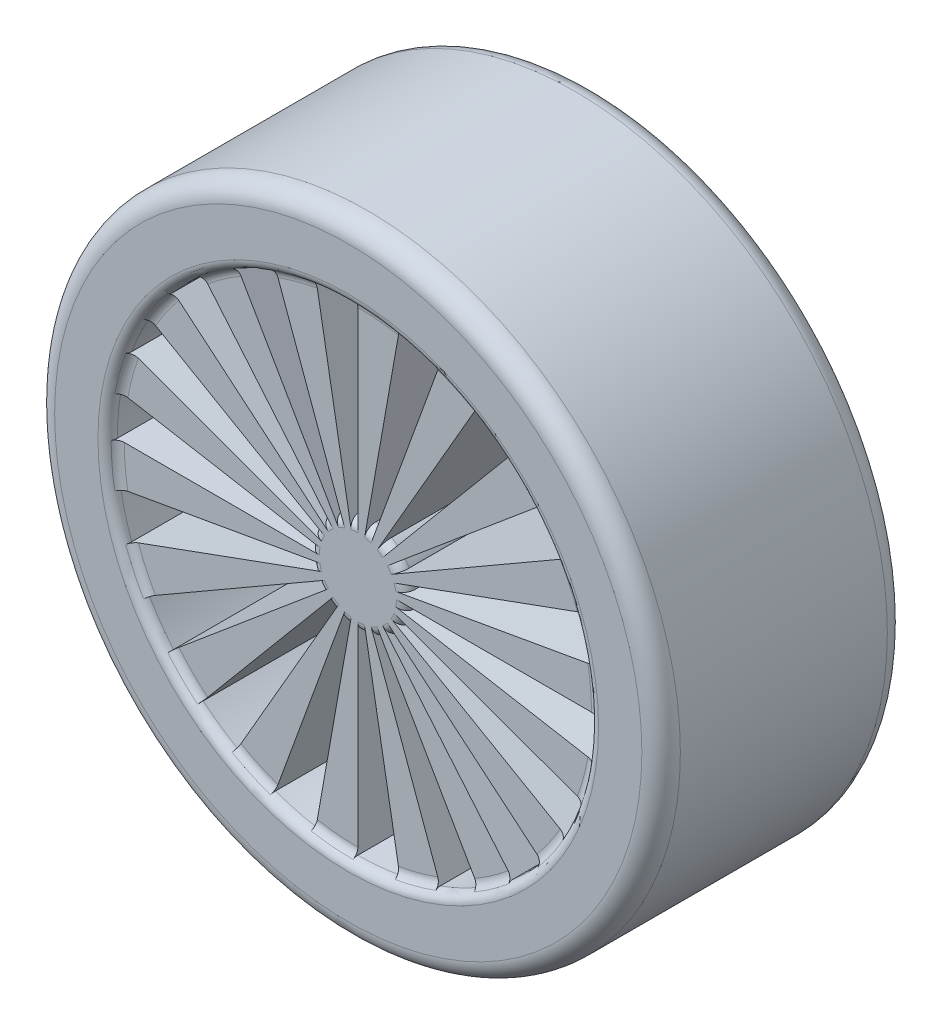
SolidWorks part; units mm, degrees
ref_plane "前视基准面" through (0, 0, 0) normal (0, 0, 1) x (1, 0, 0)
ref_plane "上视基准面" through (0, 0, 0) normal (0, 1, 0) x (1, 0, 0)
ref_plane "右视基准面" through (0, 0, 0) normal (1, 0, 0) x (0, 0, -1)
sketch "草图1" plane through (0, 0, 0) normal (0, 0, 1) x (1, 0, 0)
  circle A0 centre (0, 0) radius 32.5
  dimension "D1" = 65
extrude "凸台-拉伸1" add sketch "草图1" along normal blind 25.5
fillet "圆角1" radius 2 2 edges at (32.5, 0, 25.5) (32.5, 0, 0)
sketch "草图2" plane through (0, 0, 0) normal (0, 0, -1) x (-1, 0, 0)
  circle A0 centre (0, 0) radius 25
  dimension "D1" = 50
extrude "切除-拉伸1" cut sketch "草图2" against normal blind 8 contours A0
fillet "圆角2" radius 1 1 edges at (-25, 0, 0)
sketch "草图3" plane through (0, 0, 8) normal (0, 0, -1) x (-1, 0, 0)
  line L0 (0, 5) -> (0, 25)
  line L1 (0.8682, 4.924) -> (4.3412, 24.6202)
  line L2 (0.8682, 4.924) -> (0, 0) construction
  line L3 (1.7101, 4.6985) -> (8.5505, 23.4923)
  line L4 (2.5, 4.3301) -> (12.5, 21.6506)
  line L5 (3.2139, 3.8302) -> (16.0697, 19.1511)
  line L6 (3.8302, 3.2139) -> (19.1511, 16.0697)
  line L7 (4.3301, 2.5) -> (21.6506, 12.5)
  line L8 (4.6985, 1.7101) -> (23.4923, 8.5505)
  line L9 (4.924, 0.8682) -> (24.6202, 4.3412)
  line L10 (5, 0) -> (25, 0)
  line L11 (4.924, -0.8682) -> (24.6202, -4.3412)
  line L12 (4.6985, -1.7101) -> (23.4923, -8.5505)
  line L13 (4.3301, -2.5) -> (21.6506, -12.5)
  line L14 (3.8302, -3.2139) -> (19.1511, -16.0697)
  line L15 (3.2139, -3.8302) -> (16.0697, -19.1511)
  line L16 (2.5, -4.3301) -> (12.5, -21.6506)
  line L17 (1.7101, -4.6985) -> (8.5505, -23.4923)
  line L18 (0.8682, -4.924) -> (4.3412, -24.6202)
  line L19 (0, -5) -> (0, -25)
  line L20 (-0.8682, -4.924) -> (-4.3412, -24.6202)
  line L21 (-1.7101, -4.6985) -> (-8.5505, -23.4923)
  line L22 (-2.5, -4.3301) -> (-12.5, -21.6506)
  line L23 (-3.2139, -3.8302) -> (-16.0697, -19.1511)
  line L24 (-3.8302, -3.2139) -> (-19.1511, -16.0697)
  line L25 (-4.3301, -2.5) -> (-21.6506, -12.5)
  line L26 (-4.6985, -1.7101) -> (-23.4923, -8.5505)
  line L27 (-4.924, -0.8682) -> (-24.6202, -4.3412)
  line L28 (-5, 0) -> (-25, 0)
  line L29 (-4.924, 0.8682) -> (-24.6202, 4.3412)
  line L30 (-4.6985, 1.7101) -> (-23.4923, 8.5505)
  line L31 (-4.3301, 2.5) -> (-21.6506, 12.5)
  line L32 (-3.8302, 3.2139) -> (-19.1511, 16.0697)
  line L33 (-3.2139, 3.8302) -> (-16.0697, 19.1511)
  line L34 (-2.5, 4.3301) -> (-12.5, 21.6506)
  line L35 (-1.7101, 4.6985) -> (-8.5505, 23.4923)
  line L36 (-0.8682, 4.924) -> (-4.3412, 24.6202)
  arc A0 (-0.8682, 4.924) -> (-1.7101, 4.6985) centre (0, 0) ccw
  circle A1 centre (0, 0) radius 25 construction
  arc A2 (4.3412, 24.6202) -> (0, 25) centre (0, 0) ccw
  arc A3 (12.5, 21.6506) -> (8.5505, 23.4923) centre (0, 0) ccw
  arc A4 (19.1511, 16.0697) -> (16.0697, 19.1511) centre (0, 0) ccw
  arc A5 (23.4923, 8.5505) -> (21.6506, 12.5) centre (0, 0) ccw
  arc A6 (25, 0) -> (24.6202, 4.3412) centre (0, 0) ccw
  arc A7 (23.4923, -8.5505) -> (24.6202, -4.3412) centre (0, 0) ccw
  arc A8 (19.1511, -16.0697) -> (21.6506, -12.5) centre (0, 0) ccw
  arc A9 (12.5, -21.6506) -> (16.0697, -19.1511) centre (0, 0) ccw
  arc A10 (4.3412, -24.6202) -> (8.5505, -23.4923) centre (0, 0) ccw
  arc A11 (-4.3412, -24.6202) -> (0, -25) centre (0, 0) ccw
  arc A12 (-12.5, -21.6506) -> (-8.5505, -23.4923) centre (0, 0) ccw
  arc A13 (-19.1511, -16.0697) -> (-16.0697, -19.1511) centre (0, 0) ccw
  arc A14 (-23.4923, -8.5505) -> (-21.6506, -12.5) centre (0, 0) ccw
  arc A15 (-25, 0) -> (-24.6202, -4.3412) centre (0, 0) ccw
  arc A16 (-23.4923, 8.5505) -> (-24.6202, 4.3412) centre (0, 0) ccw
  arc A17 (-19.1511, 16.0697) -> (-21.6506, 12.5) centre (0, 0) ccw
  arc A18 (-12.5, 21.6506) -> (-16.0697, 19.1511) centre (0, 0) ccw
  arc A19 (-4.3412, 24.6202) -> (-8.5505, 23.4923) centre (0, 0) ccw
  arc A20 (0.8682, 4.924) -> (0, 5) centre (0, 0) ccw
  arc A21 (2.5, 4.3301) -> (1.7101, 4.6985) centre (0, 0) ccw
  arc A22 (3.8302, 3.2139) -> (3.2139, 3.8302) centre (0, 0) ccw
  arc A23 (4.6985, 1.7101) -> (4.3301, 2.5) centre (0, 0) ccw
  arc A24 (5, 0) -> (4.924, 0.8682) centre (0, 0) ccw
  arc A25 (4.6985, -1.7101) -> (4.924, -0.8682) centre (0, 0) ccw
  arc A26 (3.8302, -3.2139) -> (4.3301, -2.5) centre (0, 0) ccw
  arc A27 (2.5, -4.3301) -> (3.2139, -3.8302) centre (0, 0) ccw
  arc A28 (0.8682, -4.924) -> (1.7101, -4.6985) centre (0, 0) ccw
  arc A29 (-0.8682, -4.924) -> (0, -5) centre (0, 0) ccw
  arc A30 (-2.5, -4.3301) -> (-1.7101, -4.6985) centre (0, 0) ccw
  arc A31 (-3.8302, -3.2139) -> (-3.2139, -3.8302) centre (0, 0) ccw
  arc A32 (-4.6985, -1.7101) -> (-4.3301, -2.5) centre (0, 0) ccw
  arc A33 (-5, 0) -> (-4.924, -0.8682) centre (0, 0) ccw
  arc A34 (-4.6985, 1.7101) -> (-4.924, 0.8682) centre (0, 0) ccw
  arc A35 (-3.8302, 3.2139) -> (-4.3301, 2.5) centre (0, 0) ccw
  arc A36 (-2.5, 4.3301) -> (-3.2139, 3.8302) centre (0, 0) ccw
  point P81 (0, 0)
  dimension "D1" = 10
  dimension "D2" = 18
  dimension "D3" = 10
extrude "切除-拉伸2" cut sketch "草图3" against normal through all
sketch "草图4" plane through (0, 0, 25.5) normal (0, 0, 1) x (1, 0, 0)
  circle A0 centre (0, 0) radius 25
  dimension "D1" = 50
extrude "切除-拉伸3" cut sketch "草图4" against normal blind 1
fillet "圆角3" radius 1 1 edges at (-25, 0, 25.5)
fillet "圆角4" radius 1 18 edges at (-2.1131, 4.5315, 24.5) (-3.5355, 3.5355, 24.5) (-4.5315, 2.1131, 24.5) (-4.981, 0.4358, 24.5) (-4.8296, -1.2941, 24.5) (-4.0958, -2.8679, 24.5) (-2.8679, -4.0958, 24.5) (-1.2941, -4.8296, 24.5) (0.4358, -4.981, 24.5) (2.1131, -4.5315, 24.5) (3.5355, -3.5355, 24.5) (4.5315, -2.1131, 24.5) (4.981, -0.4358, 24.5) (4.8296, 1.2941, 24.5) (4.0958, 2.8679, 24.5) (2.8679, 4.0958, 24.5) (1.2941, 4.8296, 24.5) (-0.4358, 4.981, 24.5)
fillet "圆角5" radius 1 1 edges at (6.4705, -24.1481, 24.5)
fillet "圆角6" radius 1 17 edges at (-2.1789, -24.9049, 24.5) (-10.5655, -22.6577, 24.5) (-17.6777, -17.6777, 24.5) (-22.6577, -10.5655, 24.5) (-24.9049, -2.1789, 24.5) (-24.1481, 6.4705, 24.5) (-20.4788, 14.3394, 24.5) (-14.3394, 20.4788, 24.5) (-6.4705, 24.1481, 24.5) (2.1789, 24.9049, 24.5) (10.5655, 22.6577, 24.5) (17.6777, 17.6777, 24.5) (22.6577, 10.5655, 24.5) (24.9049, 2.1789, 24.5) (24.1481, -6.4705, 24.5) (20.4788, -14.3394, 24.5) (14.3394, -20.4788, 24.5)
sketch "草图5" plane through (0, 0, 8) normal (0, 0, -1) x (-1, 0, 0)
  circle A0 centre (0, 0) radius 4
  dimension "D1" = 8
extrude "凸台-拉伸2" add sketch "草图5" along normal blind 6
